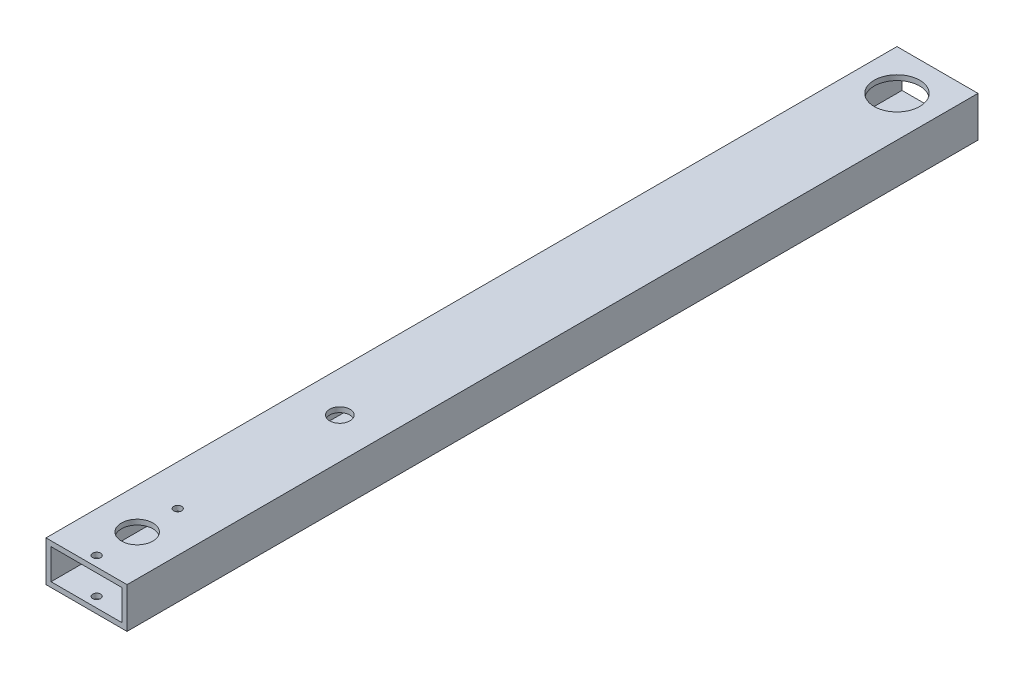
SolidWorks part; units mm, degrees
ref_plane "Front Plane" through (0, 0, 0) normal (0, 0, 1) x (1, 0, 0)
ref_plane "Top Plane" through (0, 0, 0) normal (0, 1, 0) x (1, 0, 0)
ref_plane "Right Plane" through (0, 0, 0) normal (1, 0, 0) x (0, 0, -1)
sketch "Sketch1" plane through (0, 0, 0) normal (0, 0, 1) x (1, 0, 0)
  line L1 (-25.4, -12.7) -> (25.4, -12.7)
  line L2 (-25.4, -12.7) -> (-25.4, 12.7)
  line L3 (-25.4, 12.7) -> (25.4, 12.7)
  line L4 (25.4, -12.7) -> (25.4, 12.7)
  line L5 (-25.4, -12.7) -> (25.4, 12.7) construction
  line L6 (-25.4, 12.7) -> (25.4, -12.7) construction
  point P0 (0, 0)
  dimension "D1" = 50.8
  dimension "D2" = 25.4
extrude "Boss-Extrude1" add sketch "Sketch1" along normal mid plane 533.4
sketch "Sketch2" plane through (0, 0, 266.7) normal (0, 0, 1) x (1, 0, 0)
  line L8 (22.225, -9.525) -> (22.225, 9.525)
  line L9 (22.225, 9.525) -> (-22.225, 9.525)
  line L10 (-22.225, 9.525) -> (-22.225, -9.525)
  line L11 (-22.225, -9.525) -> (22.225, -9.525)
  line L12 (22.225, -9.525) -> (22.225, 9.525)
  line L13 (22.225, 9.525) -> (-22.225, 9.525)
  line L14 (-22.225, 9.525) -> (-22.225, -9.525)
  line L15 (-22.225, -9.525) -> (22.225, -9.525)
  dimension "D1" = 3.175
extrude "Cut-Extrude1" cut sketch "Sketch2" against normal through all
sketch "Sketch5" plane through (0, 12.7, 0) normal (0, 1, 0) x (1, 0, 0)
  line L0 (25.4, -266.7) -> (25.4, 266.7) construction
  line L3 (0, 241.3) -> (0, -234.95) construction
  line L4 (22.225, -266.7) -> (-22.225, -266.7) construction
  circle A0 centre (0, -260.35) radius 2.4892
  circle A1 centre (0, -234.95) radius 9.8488
  circle A2 centre (0, -209.55) radius 2.4892
  circle A3 centre (0, 241.3) radius 14.2875
  point P14 (0, -266.7)
  dimension "D1" = 28.575
  dimension "D2" = 25.4
  dimension "D5" = 4.9784
  dimension "D6" = 19.6977
  dimension "D7" = 4.9784
  dimension "D8" = 25.4
  dimension "D3" = 476.25
  dimension "D9" = 25.4
  dimension "D10" = 6.35
extrude "Cut-Extrude2" cut sketch "Sketch5" against normal blind 508
sketch "Sketch7" plane through (0, 12.7, 0) normal (0, 1, 0) x (1, 0, 0)
  line L0 (-25.4, -266.7) -> (-25.4, 266.7) construction
  circle A0 centre (0, -107.95) radius 6.35
  circle A1 centre (0, -234.95) radius 9.8488 construction
  dimension "D1" = 12.7
  dimension "D2" = 127
  dimension "D3" = 25.4
extrude "Cut-Extrude4" cut sketch "Sketch7" against normal through all
